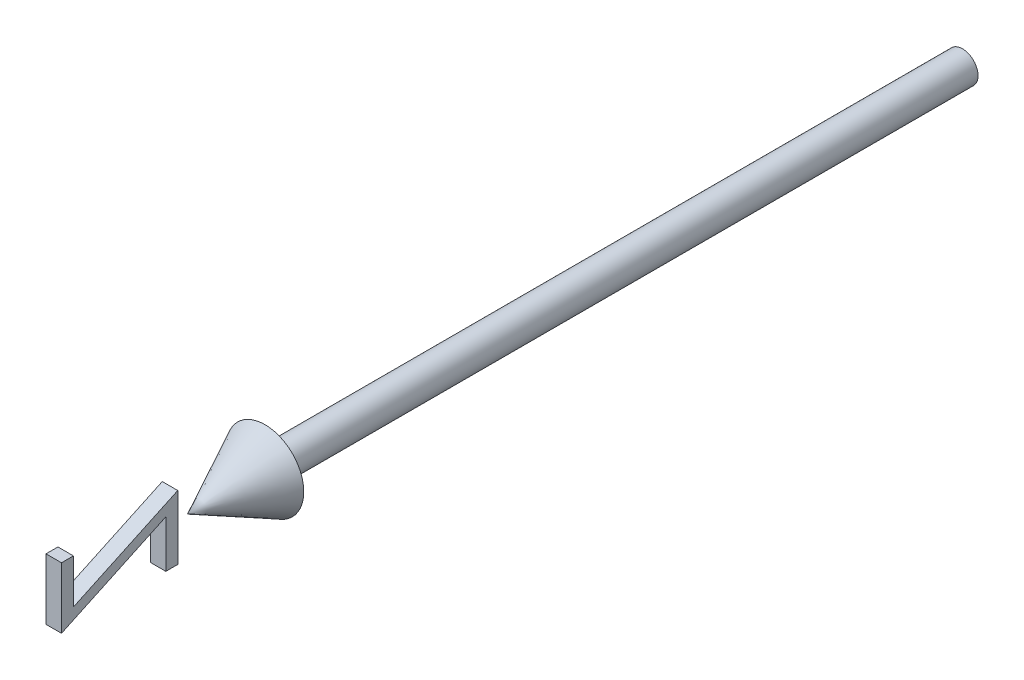
SolidWorks part; units mm, degrees
ref_plane "Front Plane" through (0, 0, 0) normal (0, 0, 1) x (1, 0, 0)
ref_plane "Top Plane" through (0, 0, 0) normal (0, 1, 0) x (1, 0, 0)
ref_plane "Right Plane" through (0, 0, 0) normal (1, 0, 0) x (0, 0, -1)
sketch "Sketch2" plane through (0, 0, 0) normal (0, 1, 0) x (1, 0, 0)
  line L0 (0, 41.95) -> (0, -114.4521) construction
  line L1 (-36.8894, 0) -> (41.4965, 0) construction
  line L2 (0, -100) -> (5, -90)
  line L3 (5, -90) -> (2, -90)
  line L4 (2, -90) -> (2, 0)
  line L5 (2, 0) -> (0, 0)
  line L6 (0, 0) -> (0, -100)
  dimension "D1" = 100
  dimension "D2" = 2
  dimension "D3" = 10
  dimension "D4" = 5
revolve "Revolve1" add sketch "Sketch2" angle 360 about L0
sketch "Sketch3" plane through (0, 0, 0) normal (1, 0, 0) x (0, -1, 0)
  line L0 (0, -101.5706) -> (0, -127.8138) construction
  line L1 (-4.8486, -102.2607) -> (14.1256, -102.2607) construction
  text T0 "Z" font "Century Gothic" height 15
  point P6 (9.5968, -105.7745)
  point P7 (-6.5664, -105.306)
  point P8 (14.1256, -104.9156)
  point P9 (-3.9116, -104.7594)
  point P10 (-6.0198, -102.8073)
  point P11 (-4.4582, -104.2909)
  point P12 (0, 0)
  point P13 (0, 0)
  point P14 (-4.8486, -104.1347)
extrude "Boss-Extrude1" add sketch "Sketch3" against normal blind 1 and the other way blind 1 separate body
equation "\"frame_arrow_length\"=100"
equation "\"D1@Sketch2\"=\"frame_arrow_length\""
equation "\"frame_arrow_odA\"=4"
equation "\"D2@Sketch2\"=\"frame_arrow_odA\"/2"
equation "\"frame_arrow_head_od\"=5"
equation "\"D4@Sketch2\"=\"frame_arrow_head_od\""
equation "\"frame_arrow_head_length\"=10"
equation "\"D3@Sketch2\"=\"frame_arrow_head_length\""
equation "\"tvarobot_theta1\"=30"
equation "\"link0_ringA_odA\"= 40"
equation "\"link0_ringA_odB\"= 25"
equation "\"link0_ringA_id\"= 20"
equation "\"link0_ringA_thickness\"= (\"link0_ringA_odB\" - \"link0_ringA_id\")/2"
equation "\"link0_ringA_height\"= 3"
equation "\"link0_ringA_heightA\"= 1.5"
equation "\"link0_ringA_heightB\"=\"link0_ringA_height\"-\"link0_ringA_heightA\""
equation "\"link0_ringB_odA\"= 40"
equation "\"link0_ringB_odB\"= 29"
equation "\"link0_ringB_id\"= \"link0_shaftA_bearing_id\"+1"
equation "\"link0_ringB_thickness\"= (\"link0_ringB_odB\" - \"link0_ringB_id\")/2"
equation "\"link0_ringB_height\"= 3"
equation "\"link0_ringB_heightA\"= 1.5"
equation "\"link0_ringB_heightB\"=\"link0_ringB_height\"-\"link0_ringB_heightA\""
equation "\"link0_shaftA_bearing_od\"=27"
equation "\"link0_shaftA_bearing_id\"=20"
equation "\"link0_shaftA_thrust_bearing_od\"=35"
equation "\"link0_shaftA_thrust_bearing_id\"=20.04"
equation "\"link0_shaftA_retaining_ring_id\"=18.5"
equation "\"link0_shaftA_retaining_ring_groove_width\"=1.5"
equation "\"link0_shaftA_spline_length\"=8.0"
equation "\"link0_shaftA_spline_depth\"=1.0"
equation "\"link0_shaftA_spline_width\"=4.0"
equation "\"link0_shaftA_odA\"=\"link0_shaftA_bearing_id\""
equation "\"link0_shaftA_odB\"=35"
equation "\"link0_shaftA_odC\"=\"link0_shaftA_bearing_id\""
equation "\"link0_shaftA_odD\"=\"link0_shaftA_odC\"-2*\"link0_shaftA_spline_depth\""
equation "\"link0_shaftA_odE\"=\"link0_shaftA_bearing_id\""
equation "\"link0_shaftA_odF\"=\"link0_shaftA_odE\"-2*\"link0_shaftA_spline_depth\""
equation "\"link0_shaftA_idA\"=10"
equation "\"link0_shaftA_idB\"=6"
equation "\"link0_shaftA_length\"=39.5"
equation "\"link0_shaftA_lengthA\"=8.0"
equation "\"link0_shaftA_lengthB\"=12.0"
equation "\"link0_shaftA_lengthC\"=35.0"
equation "\"link0_shaftA_lengthD\"=39.0"
equation "\"link0_shaftA_lengthE\"=\"link0_shaftA_length\"-\"link0_shaftA_lengthD\""
equation "\"link0_shaftA_offsetX\"=11"
equation "\"link0_shaftA_offsetY\"=0"
equation "\"link0_shaftA_bolt_pattern_dia\"=14"
equation "\"link0_motor_center_dist\"=26"
equation "\"link0_46t_pulley_spline_length\"=8"
equation "\"link0_46t_pulley_spline_depth\"=\"link0_shaftA_spline_depth\"*1.025"
equation "\"link0_46t_pulley_spline_width\"=\"link0_shaftA_spline_width\"*1.05"
equation "\"link0_46t_pulley_idA\"=\"link0_shaftA_bearing_id\"*1.025"
equation "\"link0_46t_pulley_idB\"=\"link0_46t_pulley_idA\"-2*\"link0_46t_pulley_spline_depth\""
equation "\"link0_shaftB_spline_length\"=10"
equation "\"link0_shaftB_spline_depth\"=1.0"
equation "\"link0_shaftB_spline_width\"=1.25"
equation "\"link0_shaftB_length\"=7"
equation "\"link0_shaftB_lengthA\"=1.5"
equation "\"link0_shaftB_lengthB\"=2.75"
equation "\"link0_shaftB_odA\"=32"
equation "\"link0_shaftB_odB\"=22"
equation "\"link0_shaftB_odC\"=20"
equation "\"link0_shaftB_idA\"=10"
equation "\"link0_shaftB_bolt_diameter\"=19"
equation "\"link0_shaftB_bearing_od\"=27"
equation "\"link0_shaftB_bearing_id\"=20"
equation "\"link0_motor_length\"=46.5"
equation "\"link0_motor_width\"=28.5"
equation "\"link0_motor_height\"=34"
equation "\"link0_motor_offset\"=8"
equation "\"link0_shellA_thickness\"=2.5"
equation "\"link0_shellB_thickness\"=\"link0_shellA_thickness\""
equation "\"link0_plateA_shellA_height\"=48"
equation "\"link0_shellA_width\" =\"link0_plateA_width\""
equation "\"link0_shellA_height\" = \"link0_plateA_shellA_height\"-\"link0_plateA_height\""
equation "\"link0_shellA_length\" = \"link0_plateA_lengthB\" "
equation "\"link0_shellB_length\"=\"link0_shellA_length\""
equation "\"link0_shellA_radius\" = 0.375*25.4"
equation "\"link0_shellA_radiusA\"= \"link0_plateA_radiusA\""
equation "\"link0_shellA_radiusB\"= \"link0_plateA_radiusB\""
equation "\"link0_shellA_radiusC\"= 3"
equation "\"link0_postA_height\"=7"
equation "\"link0_postA_width\"=16"
equation "\"link0_postA_length\"=20"
equation "\"link0_postA_posX\"=22"
equation "\"link0_postA_posY\"=17.5"
equation "\"link0_postA_pocket_width\"=6.0"
equation "\"link0_postA_pocket_length\"=2.5"
equation "\"link0_postA_pocket_depth\"=9"
equation "\"link0_postA_pocket_posZ\"=10"
equation "\"link0_postB_height\"=7"
equation "\"link0_postB_width\"=16"
equation "\"link0_postB_length\"=20"
equation "\"link0_postB_posX\"=22"
equation "\"link0_postB_posY\"=17.5"
equation "\"link0_postB_id\"=3.0"
equation "\"link0_postB_pocket_width\"=6.0"
equation "\"link0_postB_pocket_length\"=2.5"
equation "\"link0_postB_pocket_depth\"=9"
equation "\"link0_postB_pocket_posZ\"=10"
equation "\"link0_postC_height\"=7"
equation "\"link0_postC_width\"=16"
equation "\"link0_postC_length\"=20"
equation "\"link0_postC_posX\"=22"
equation "\"link0_postC_posY\"=17.5"
equation "\"link0_postC_id\"=3.0"
equation "\"link0_postC_pocket_width\"=6.0"
equation "\"link0_postC_pocket_length\"=2.5"
equation "\"link0_postC_pocket_depth\"=9"
equation "\"link0_postC_pocket_posZ\"=10"
equation "\"link0_postD_height\"=7"
equation "\"link0_postD_width\"=16"
equation "\"link0_postD_length\"=20"
equation "\"link0_postD_posX\"=22"
equation "\"link0_postD_posY\"=17.5"
equation "\"link0_postD_id\"=3.0"
equation "\"link0_postD_pocket_width\"=6.0"
equation "\"link0_postD_pocket_length\"=3.0"
equation "\"link0_postD_pocket_depth\"=9"
equation "\"link0_postD_pocket_posZ\"=10"
equation "\"link0_postE_height\"=5"
equation "\"link0_postE_width\"=16"
equation "\"link0_postE_length\"=\"link0_plateE_lengthA\"-\"link0_lip_height\""
equation "\"link0_postE_posZ\"=22"
equation "\"link0_postE_posX\"=17.5"
equation "\"link0_postE_posY\"=22"
equation "\"link0_postE_id\"=3.0"
equation "\"link0_postE_cbore_id\"=6.5"
equation "\"link0_postE_hole_id\"=3"
equation "\"link0_postF_posZ\"=22"
equation "\"link0_postF_posX\"=17.5"
equation "\"link0_postF_posY\"=\"link0_plateB_lengthA\"+4"
equation "\"link0_postF_id\"=3.0"
equation "\"link0_postF_cbore_id\"=6.5"
equation "\"link0_postF_hole_id\"=3"
equation "\"link0_postG_posZ\"=22"
equation "\"link0_postG_posX\"=17.5"
equation "\"link0_postG_posY\"=\"link0_plateB_lengthA\"+12"
equation "\"link0_postG_id\"=3.0"
equation "\"link0_postG_cbore_id\"=6.5"
equation "\"link0_postG_hole_id\"=3"
equation "\"link0_postHIJ_posY\"=6"
equation "\"link0_postH_posX\"=28"
equation "\"link0_postH_posY\"=20"
equation "\"link0_postH_posZ\"=20"
equation "\"link0_postH_length\"=10"
equation "\"link0_postI_posX\"=28"
equation "\"link0_postI_posY\"=20"
equation "\"link0_postI_posZ\"=135"
equation "\"link0_postI_length\"=10"
equation "\"link0_postJ_posX\"=28"
equation "\"link0_postJ_posY\"=20"
equation "\"link0_postJ_posZ\"=175"
equation "\"link0_postJ_length\"=10"
equation "\"link0_postK_posX\"=28"
equation "\"link0_postK_posY\"=20"
equation "\"link0_postK_posZ\"=175"
equation "\"link0_postK_length\"=10"
equation "\"link0_postL_posX\"=28"
equation "\"link0_postL_posY\"=20"
equation "\"link0_postL_posZ\"=135"
equation "\"link0_postL_length\"=10"
equation "\"link0_postM_posX\"=28"
equation "\"link0_postM_posY\"=20"
equation "\"link0_postM_posZ\"=35"
equation "\"link0_postM_length\"=10"
equation "\"link0_plateA_lengthA\"=30"
equation "\"link0_plateA_lengthB\"=150"
equation "\"link0_plateA_lengthC\"=30"
equation "\"link0_plateA_length\"=\"link0_plateA_lengthA\"+\"link0_plateA_lengthB\"+\"link0_plateA_lengthC\""
equation "\"link0_plateA_width\"=  68"
equation "\"link0_plateA_height\"= \"link0_plateA_radiusA\""
equation "\"link0_plateA_thickness\"=\"link0_shellA_thickness\""
equation "\"link0_plateA_radius\"= 9.5"
equation "\"link0_plateA_radiusA\"= 18"
equation "\"link0_plateA_radiusB\"= 18"
equation "\"link0_plateA_radiusC\"= 3"
equation "\"link0_plateB_length\"= 40"
equation "\"link0_plateB_width\"= \"link0_plateA_width\"*1.005"
equation "\"link0_plateB_height\"= \"link0_plateA_shellA_height\"*1.005"
equation "\"link0_plateB_lengthA\"=\"link0_lip_height\"+\"link0_plateD_thickness\"+\"link0_motor_mount_thickness\""
equation "\"link0_plateB_lengthB\"=\"link0_plateB_height\"-\"link0_plateB_lengthA\""
equation "\"link0_plateB_radiusA\"= \"link0_plateA_radiusA\""
equation "\"link0_plateB_radiusB\"= \"link0_plateA_radiusB\""
equation "\"link0_plateB_radiusC\"= 3"
equation "\"link0_plateB_idA\"=\"link0_shaftA_odC\"+1"
equation "\"link0_plateB_idB\"=\"link0_shaftA_bearing_od\"-2"
equation "\"link0_plateB_idC\"=\"link0_shaftA_bearing_od\"*1.005"
equation "\"link0_plateB_idD\"=\"link0_shaftA_thrust_bearing_od\"+1 "
equation "\"link0_plateB_depthA\"=1.0"
equation "\"link0_plateB_depthB\"=2.0"
equation "\"link0_plateB_depthC\"=8"
equation "\"link0_plateB_depthD\"=\"link0_plateB_length\"-\"link0_lip_height\"-\"link0_plateD_thickness\" "
equation "\"link0_plateC_length\"=\"link0_plateB_length\""
equation "\"link0_plateC_width\"= \"link0_plateB_width\""
equation "\"link0_plateC_height\"= .1*25.4"
equation "\"link0_plateA_hole_od\" = 0.1*25.4"
equation "\"link0_plateA_hole_delx\" = 0.5*25.4"
equation "\"link0_plateA_hole_delz\" = 0.75*25.4"
equation "\"link0_plateA_hole_offx\" = 0.0*25.4"
equation "\"link0_plateA_hole_offz\" = \"link0_plateA_length\"/2"
equation "\"link0_plateB_hole_od\" = 0.1*25.4"
equation "\"link0_plateB_hole_delx\"= 0.75*25.4"
equation "\"link0_plateB_hole_delz\"= 0.75*25.4"
equation "\"link0_plateB_hole_offx\"= 0.0*25.4"
equation "\"link0_plateB_hole_offz\"= 0.0*25.4"
equation "\"link0_plateC_hole_od\"= 0.1*25.4"
equation "\"link0_plateC_hole_delx\"= 0.75*25.4"
equation "\"link0_plateC_hole_delz\"= 0.75*25.4"
equation "\"link0_plateC_hole_offx\"= 0.0*25.4"
equation "\"link0_plateC_hole_offz\"= 0.0*25.4"
equation "\"link0_plateD_height\"=\"link0_plateB_height\"-2*\"link0_shellA_thickness\""
equation "\"link0_plateD_width\"=\"link0_plateB_width\"-2*\"link0_shellA_thickness\""
equation "\"link0_plateD_thickness\"=10"
equation "\"link0_plateD_radiusA\"=\"link0_plateB_radiusA\"-\"link0_shellA_thickness\""
equation "\"link0_plateD_odA\"= .375*25.4"
equation "\"link0_plateD_odB\"= .375*25.4"
equation "\"link0_plateD_bearing_id\"=20"
equation "\"link0_plateD_bearing_od\"=27"
equation "\"link0_plateE_radiusA\"=\"link0_plateA_radiusA\""
equation "\"link0_plateE_radiusB\"=\"link0_plateA_radiusB\""
equation "\"link0_plateE_radiusC\"=8.0"
equation "\"link0_plateE_length\"=30"
equation "\"link0_plateE_lengthA\"=16"
equation "\"link0_plateE_height\"=\"link0_plateB_height\""
equation "\"link0_plateE_width\"=\"link0_plateB_width\""
equation "\"link0_plateE_odA\"=\"gantry_coupler_id\"*0.99"
equation "\"link0_plateE_idA\"=\"link0_plateE_odA\"-20.0"
equation "\"link0_plateE_spline_depth\"=\"link0_poleA_spline_depth\"*1.05"
equation "\"link0_plateE_spline_width\"=\"link0_poleA_spline_width\"*1.075"
equation "\"link0_plateE_spline_length\"=\"link0_poleA_spline_length\""
equation "\"link0_plateE_coupler_length\"=46"
equation "\"link0_lip_height\"=5.0"
equation "\"link0_lip_thickness\"=2.0"
equation "\"link0_motor_mount_thickness\"=8.0"
equation "\"link0_motor_mount_idA\"=22"
equation "\"link0_motor_mount_idB\"=\"link0_shaftB_bearing_od\"*1.005"
equation "\"link0_motor_mount_idC\"=\"link0_shaftB_bearing_od\"-2"
equation "\"link0_motor_mount_depthA\"=5.5"
equation "\"link0_motor_mount_height\"=\"link0_plateD_height\""
equation "\"link0_motor_mount_width\"=\"link0_plateD_width\""
equation "\"link0_motor_mountL_height\"=36"
equation "\"link0_motor_mountL_heightA\"=12"
equation "\"link0_motor_mountL_length\"=50"
equation "\"link0_motor_mountL_lengthA\"=36"
equation "\"gantry_coupler_od\"=25.4*2.0"
equation "\"gantry_coupler_id\"=1.645*25.4"
equation "\"gantry_coupler_offsetX\"=\"link0_plateE_width\"/2"
equation "\"link0_poleA_odA\"=20"
equation "\"link0_poleA_odB\"=36"
equation "\"link0_poleA_idA\"=\"link0_poleA_odA\"-2*\"link0_poleA_thickness\""
equation "\"link0_poleA_idB\"=(\"link0_plateE_idA\"/2+1.5*\"link0_lip_thickness\")*1.04"
equation "\"link0_poleA_thickness\"=3.5"
equation "\"link0_poleA_length\"=100"
equation "\"link0_poleA_lengthA\"=18.5"
equation "\"link0_poleA_lengthB\"=80"
equation "\"link0_poleA_gasket_thickness\"=1.5"
equation "\"link0_poleA_spline_depth\"=1.0"
equation "\"link0_poleA_spline_width\"=4.0"
equation "\"link0_poleA_spline_length\"=10.0"
equation "\"link1_plateB_length\"=30"
equation "\"link1_lip_height\"=\"link0_lip_height\""
equation "\"link0_tension_plateA_width\"=12"
equation "\"link0_tension_plateA_lengthA\"=10.5"
equation "\"link0_tension_plateB_width\"=\"link0_tension_plateA_width\""
equation "\"link0_tension_plateB_lengthA\"=\"link0_tension_plateA_lengthA\""
equation "\"link0_tension_wheelA_posZ\"=7"
equation "\"link0_tension_wheelA_posX\"=\"link0_plateD_height\"/2-\"link0_tension_plateA_lengthA\""
equation "\"link0_m2_clear_hole_id\"=2.35"
equation "\"link0_m2_insert_hole_id\"=2.5"
equation "\"link0_m2_tap_hole_id\"=1.75"
equation "\"link0_m2_nut_socket_width\"=4.25"
equation "\"link0_m2_nut_socket_depth\"=2.5"
equation "\"link0_m2_cbore_id\"=3.75"
equation "\"link0_m2_cbore_depth\"=7"
equation "\"link0_m2_5_clear_hole_id\"=2.75"
equation "\"link0_m2_5_insert_hole_id\"=2.75"
equation "\"link0_m2_5_tap_hole_id\"=2.25"
equation "\"link0_m2_5_nut_socket_width\"=5.25"
equation "\"link0_m2_5_nut_socket_depth\"=2.5"
equation "\"link0_m2_5_cbore_id\"=4.75"
equation "\"link0_m2_5_cbore_depth\"=2.5"
equation "\"link0_m2_5_insert_access_length\"=6.0"
equation "\"link0_m2_5_insert_access_width\"=3.0"
equation "\"link0_m3_clear_hole_id\"=3.25"
equation "\"link0_m3_insert_hole_id\"=3"
equation "\"link0_m3_tap_hole_id\"=2.75"
equation "\"link0_m3_nut_socket_width\"=5.75"
equation "\"link0_m3_nut_socket_depth\"=4.0"
equation "\"link0_m3_cbore_id\"=5.75"
equation "\"link0_m3_cbore_depth\"=3.5"
equation "\"link0_m3_insert_access_length\"=4.5"
equation "\"link0_m3_insert_access_width\"=3.5"
equation "\"link0_rpi_mount_height\"=6"
equation "\"link0_rpi_mount_width\"=49"
equation "\"link0_rpi_mount_length\"=58"
equation "\"link0_rpi_mount_post_od\"=6"
equation "\"link0_rpi_mount_posZ\"=72"
equation "\"link0_rpi_mount_posX\"=11.5"
equation "\"link0_mcu_mount_height\"=5"
equation "\"link0_mcu_mount_width\"=49"
equation "\"link0_mcu_mount_length\"=58"
equation "\"link0_mcu_mount_post_od\"=6"
equation "\"link0_mcu_mount_posZ\"=164"
equation "\"link0_mcu_mount_posX\"=4"
equation "\"link0_pwr_mount_height\"=4"
equation "\"link0_pwr_mount_width\"=15.75"
equation "\"link0_pwr_mount_length\"=75.75"
equation "\"link0_pwr_mount_post_od\"=6"
equation "\"link0_pwr_mount_posZ\"=75"
equation "\"link0_pwr_mount_posX\"=16"
equation "\"link0_pwr_board_height\"=6"
equation "\"link0_pwr_board_width\"=21"
equation "\"link0_pwr_board_length\"=80"
